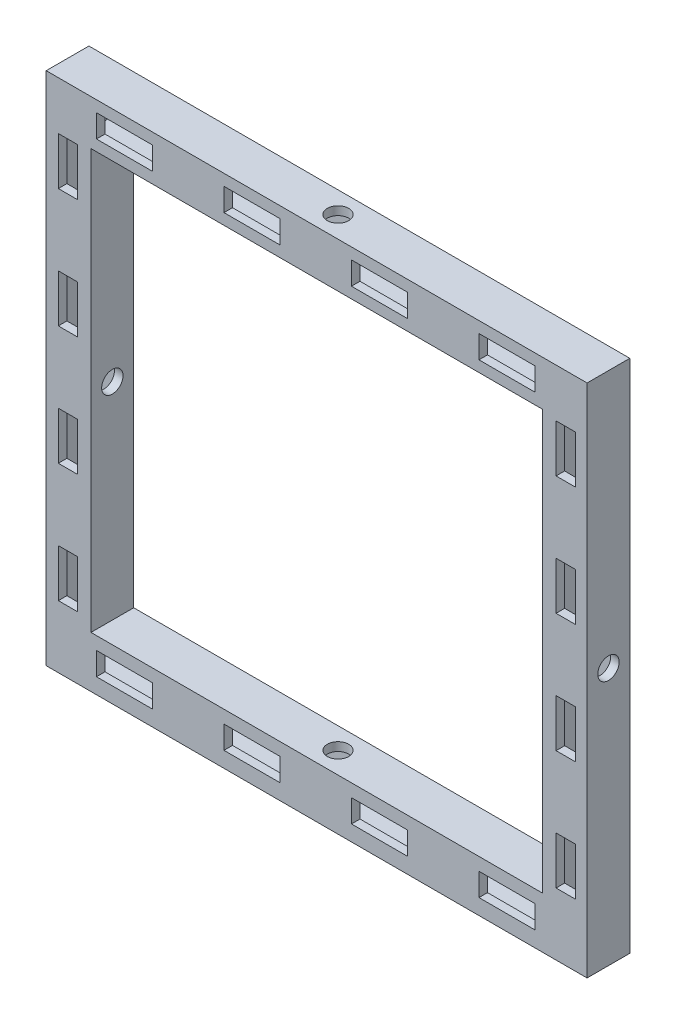
SolidWorks part; units mm, degrees
material "1060 Alloy"
ref_plane "Front Plane" through (0, 0, 0) normal (0, 0, 1) x (1, 0, 0)
ref_plane "Top Plane" through (0, 0, 0) normal (0, 1, 0) x (1, 0, 0)
ref_plane "Right Plane" through (0, 0, 0) normal (1, 0, 0) x (0, 0, -1)
sketch "Sketch1" plane through (0, 0, 0) normal (0, 0, 1) x (1, 0, 0)
  line L1 (-16.7627, 611.1626) -> (626.3627, 611.1626)
  line L2 (-16.7627, 611.1626) -> (-16.7627, -1.5626)
  line L3 (-16.7627, -1.5626) -> (626.3627, -1.5626)
  line L4 (626.3627, 611.1626) -> (626.3627, -1.5626)
  line L5 (-16.7627, 611.1626) -> (626.3627, -1.5626) construction
  line L6 (-16.7627, -1.5626) -> (626.3627, 611.1626) construction
  point P4 (304.8, 304.8)
extrude "Boss-Extrude1" add sketch "Sketch1" along normal blind 50.8
sketch "Sketch3" plane through (0, 0, 50.8) normal (0, 0, 1) x (1, 0, 0)
  line L1 (36.49, 557.5822) -> (573.0545, 557.5822)
  line L2 (36.49, 557.5822) -> (36.49, 59.3437)
  line L3 (36.49, 59.3437) -> (573.0545, 59.3437)
  line L4 (573.0545, 557.5822) -> (573.0545, 59.3437)
  line L5 (36.49, 557.5822) -> (573.0545, 59.3437) construction
  line L6 (36.49, 59.3437) -> (573.0545, 557.5822) construction
  point P0 (304.7723, 308.4629)
extrude "Cut-Extrude2" cut sketch "Sketch3" against normal blind 50.8
shell "Shell5" thickness 10.16
sketch "Sketch7" plane through (0, 0, 50.8) normal (0, 0, 1) x (1, 0, 0)
  line L1 (43.0092, 597.7876) -> (109.6846, 597.7876)
  line L2 (43.0092, 597.7876) -> (43.0092, 570.6936)
  line L3 (43.0092, 570.6936) -> (109.6846, 570.6936)
  line L4 (109.6846, 597.7876) -> (109.6846, 570.6936)
  line L5 (43.0092, 597.7876) -> (109.6846, 570.6936) construction
  line L6 (43.0092, 570.6936) -> (109.6846, 597.7876) construction
extrude "Cut-Extrude3" cut sketch "Sketch7" against normal blind 50.8
pattern_linear "LPattern1" count 4 spacing 151.6 along (1, 0, 0) count 2 spacing 553.72 along (0, -1, 0) of "Cut-Extrude3"
sketch "Sketch8" plane through (0, 0, 50.8) normal (0, 0, 1) x (1, 0, 0)
  line L1 (-2.3219, 553.6888) -> (20.5802, 553.6888)
  line L2 (-2.3219, 553.6888) -> (-2.3219, 496.9809)
  line L3 (-2.3219, 496.9809) -> (20.5802, 496.9809)
  line L4 (20.5802, 553.6888) -> (20.5802, 496.9809)
  line L5 (-2.3219, 553.6888) -> (20.5802, 496.9809) construction
  line L6 (-2.3219, 496.9809) -> (20.5802, 553.6888) construction
extrude "Cut-Extrude4" cut sketch "Sketch8" against normal blind 50.8
pattern_linear "LPattern2" count 4 spacing 141.44 along (0, -1, 0) count 2 spacing 591.82 along (1, 0, 0) of "Cut-Extrude4"
sketch "Sketch11" plane through (0, 611.1626, 0) normal (0, 1, 0) x (1, 0, 0)
  circle A0 centre (304.8, -25.4) radius 12.7
extrude "Cut-Extrude5" cut sketch "Sketch11" against normal blind 635
sketch "Sketch12" plane through (626.3627, 0, 0) normal (1, 0, 0) x (0, 0, -1)
  circle A0 centre (-25.4, 304.8) radius 12.7
sketch "Sketch13" plane through (0, 611.1626, 0) normal (0, 1, 0) x (1, 0, 0)
  circle A0 centre (308.356, -25.4) radius 12.7
extrude "Cut-Extrude7" cut sketch "Sketch12" against normal blind 660.4
